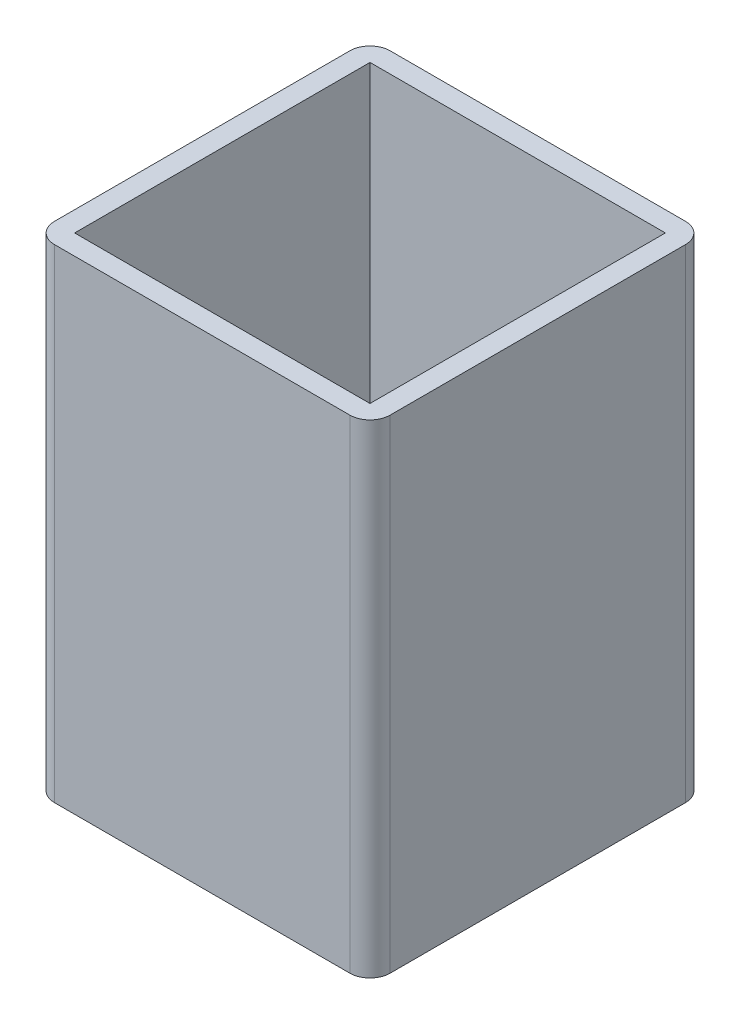
SolidWorks part; units mm, degrees
ref_plane "前视基准面" through (0, 0, 0) normal (0, 0, 1) x (1, 0, 0)
ref_plane "上视基准面" through (0, 0, 0) normal (0, 1, 0) x (1, 0, 0)
ref_plane "右视基准面" through (0, 0, 0) normal (1, 0, 0) x (0, 0, -1)
other "Configuration Table"
sketch "草图1" plane through (0, 0, 0) normal (0, 0, 1) x (1, 0, 0)
  line L0 (0, 0) -> (50, 0)
  line L1 (50, 0) -> (50, 72)
  line L2 (50, 72) -> (0, 72)
  line L3 (0, 72) -> (0, 0)
  dimension "width" = 50
  dimension "height" = 72
extrude "Stepper_cover" add sketch "草图1" along normal blind 50
fillet "Fillet" radius 3 4 edges at (0, 36, 0) (50, 36, 0) (0, 36, 50) (50, 36, 50) tangent propagation no
shell "抽壳1" thickness 3 removed face at (25, 72, 25)
sketch "草图2" plane through (0, 0, 0) normal (0, -1, 0) x (1, 0, 0)
  circle A0 centre (25, 25) radius 12
  dimension "diameter" = 24
  dimension "x" = 25
  dimension "y" = 25
extrude "Coupler_clearance" cut sketch "草图2" against normal blind 3.1
